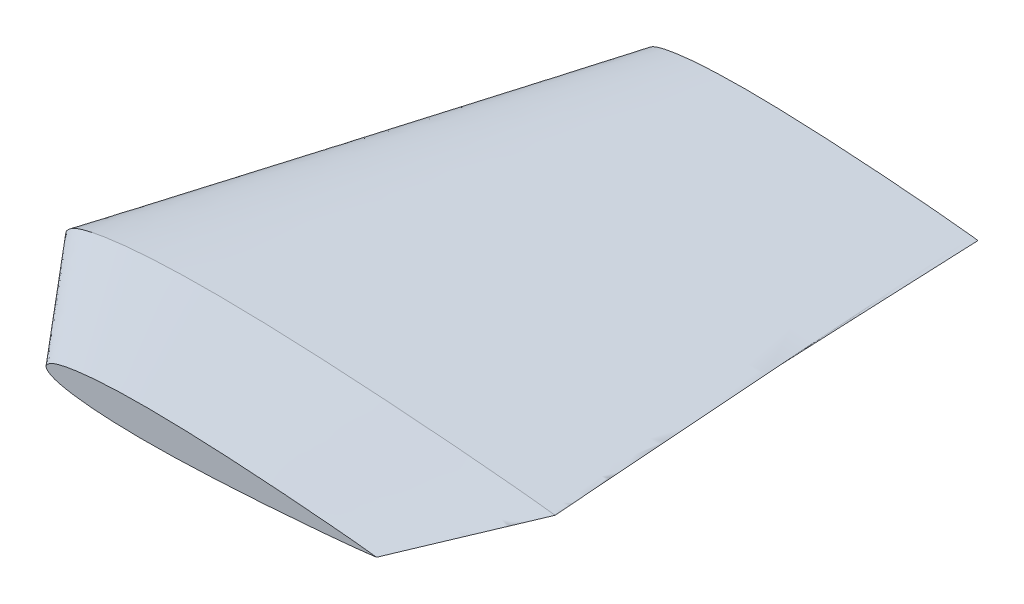
SolidWorks part; units mm, degrees
ref_plane "Front Plane" through (0, 0, 0) normal (0, 0, 1) x (1, 0, 0)
ref_plane "Top Plane" through (0, 0, 0) normal (0, 1, 0) x (1, 0, 0)
ref_plane "Right Plane" through (0, 0, 0) normal (1, 0, 0) x (0, 0, -1)
sketch "Sketch1" plane through (0, 0, 0) normal (0, 0, 1) x (1, 0, 0)
  line L0 (0, 0) -> (187.96, 0) construction
  line L1 (0, 0) -> (0, -12.4987) construction
  line L2 (0, 0) -> (-15.7902, 0) construction
  spline S0 degree 3 poles (186.243, -0.1788) (188.3915, 0) (186.243, 0.1788) (184.4821, 0.4769) (180.2047, 0.9339) (174.9493, 1.5013) (168.1015, 2.167) (160.0618, 2.9017) (150.8654, 3.6912) (140.7047, 4.5123) (129.7418, 5.3323) (118.1677, 6.1268) (106.1797, 6.8593) (93.9831, 7.4989) (81.786, 8.0074) (71.7149, 8.3011) (63.8146, 8.4361) (58.0672, 8.484) (52.4732, 8.4773) (47.0565, 8.4053) (41.8407, 8.2789) (36.8486, 8.088) (32.1012, 7.8395) (27.6181, 7.5278) (23.4185, 7.1579) (19.5216, 6.7268) (15.9436, 6.2426) (12.6986, 5.7178) (9.8001, 5.1548) (7.2575, 4.5555) (5.0828, 3.8997) (3.2807, 3.1752) (1.8678, 2.3759) (0.8518, 1.5413) (0.2172, 0.7763) (-0.0889, 0) (0.2172, -0.7763) (0.8518, -1.5413) (1.8678, -2.3759) (3.2807, -3.1752) (5.0828, -3.8997) (7.2575, -4.5555) (9.8001, -5.1548) (12.6986, -5.7178) (15.9436, -6.2426) (19.5216, -6.7268) (23.4185, -7.1579) (27.6181, -7.5278) (32.1012, -7.8395) (36.8486, -8.088) (41.8407, -8.2789) (47.0565, -8.4053) (52.4732, -8.4773) (58.0672, -8.484) (63.8146, -8.4361) (71.7149, -8.3011) (81.786, -8.0074) (93.9831, -7.4989) (106.1797, -6.8593) (118.1677, -6.1268) (129.7418, -5.3323) (140.7047, -4.5123) (150.8654, -3.6912) (160.0618, -2.9017) (168.1015, -2.167) (174.9493, -1.5013) (180.2047, -0.9339) (184.4821, -0.4769) (186.243, -0.1788) (188.3915, 0) (186.243, 0.1788) knots -0.018944 -0.008488 -0.002133 0 0.002133 0.008488 0.018944 0.033319 0.051356 0.072756 0.097141 0.124097 0.153163 0.183834 0.215589 0.247878 0.280151 0.31186 0.327333 0.342463 0.357187 0.371448 0.385183 0.398331 0.410845 0.422673 0.433769 0.44409 0.453589 0.46224 0.47001 0.476871 0.482833 0.487909 0.492155 0.495592 0.498196 0.5 0.501804 0.504408 0.507845 0.512091 0.517167 0.523129 0.52999 0.53776 0.546411 0.55591 0.566231 0.577327 0.589155 0.601669 0.614817 0.628552 0.642813 0.657537 0.672667 0.68814 0.719849 0.752122 0.784411 0.816166 0.846837 0.875903 0.902859 0.927244 0.948644 0.966681 0.981056 0.991512 0.997867 1 1.002133 1.008488 1.018944 only from (187.96, 0) to (187.96, 0)
  dimension "D1" = 187.96
ref_plane "Plane1" through (0, 0, 48.26) normal (0, 0, 1) x (1, 0, 0)
sketch "Sketch2" plane through (0, 0, 48.26) normal (0, 0, 1) x (1, 0, 0)
  line L0 (40.64, 0) -> (167.64, 0) construction
  line L1 (40.64, 0) -> (40.64, -29.8039) construction
  line L2 (40.64, 0) -> (47.4613, 0) construction
  line L3 (0, 0) -> (187.96, 0) construction
  spline S0 degree 3 poles (166.4799, -0.1208) (167.9316, 0) (166.4799, 0.1208) (165.2901, 0.3222) (162.3999, 0.631) (158.849, 1.0144) (154.2221, 1.4642) (148.7899, 1.9606) (142.5761, 2.494) (135.7108, 3.0488) (128.3034, 3.6029) (120.4831, 4.1397) (112.3831, 4.6347) (104.1421, 5.0668) (95.9008, 5.4104) (89.096, 5.6089) (83.758, 5.7) (79.8746, 5.7324) (76.0949, 5.7279) (72.4349, 5.6792) (68.9107, 5.5938) (65.5377, 5.4648) (62.33, 5.297) (59.3009, 5.0863) (56.4633, 4.8364) (53.8302, 4.5451) (51.4127, 4.218) (49.2202, 3.8634) (47.2617, 3.483) (45.5437, 3.078) (44.0743, 2.6349) (42.8567, 2.1454) (41.902, 1.6054) (41.2155, 1.0414) (40.7868, 0.5245) (40.5799, 0) (40.7868, -0.5245) (41.2155, -1.0414) (41.902, -1.6054) (42.8567, -2.1454) (44.0743, -2.6349) (45.5437, -3.078) (47.2617, -3.483) (49.2202, -3.8634) (51.4127, -4.218) (53.8302, -4.5451) (56.4633, -4.8364) (59.3009, -5.0863) (62.33, -5.297) (65.5377, -5.4648) (68.9107, -5.5938) (72.4349, -5.6792) (76.0949, -5.7279) (79.8746, -5.7324) (83.758, -5.7) (89.096, -5.6089) (95.9008, -5.4104) (104.1421, -5.0668) (112.3831, -4.6347) (120.4831, -4.1397) (128.3034, -3.6029) (135.7108, -3.0488) (142.5761, -2.494) (148.7899, -1.9606) (154.2221, -1.4642) (158.849, -1.0144) (162.3999, -0.631) (165.2901, -0.3222) (166.4799, -0.1208) (167.9316, 0) (166.4799, 0.1208) knots -0.018944 -0.008488 -0.002133 0 0.002133 0.008488 0.018944 0.033319 0.051356 0.072756 0.097141 0.124097 0.153163 0.183834 0.215589 0.247878 0.280151 0.31186 0.327333 0.342463 0.357187 0.371448 0.385183 0.398331 0.410845 0.422673 0.433769 0.44409 0.453589 0.46224 0.47001 0.476871 0.482833 0.487909 0.492155 0.495592 0.498196 0.5 0.501804 0.504408 0.507845 0.512091 0.517167 0.523129 0.52999 0.53776 0.546411 0.55591 0.566231 0.577327 0.589155 0.601669 0.614817 0.628552 0.642813 0.657537 0.672667 0.68814 0.719849 0.752122 0.784411 0.816166 0.846837 0.875903 0.902859 0.927244 0.948644 0.966681 0.981056 0.991512 0.997867 1 1.002133 1.008488 1.018944 only from (167.64, 0) to (167.64, 0)
  dimension "D1" = 127
  dimension "D2" = 40.64
ref_plane "Plane2" through (0, 0, -172.72) normal (0, 0, 1) x (1, 0, 0)
sketch "Sketch3" plane through (0, 0, -172.72) normal (0, 0, 1) x (1, 0, 0)
  line L0 (50.8, 0) -> (177.8, 0) construction
  line L1 (50.8, 0) -> (50.8, -7.5229) construction
  line L2 (50.8, 0) -> (43.7016, 0) construction
  line L3 (0, 0) -> (187.96, 0) construction
  line L5 (0, -9.3299) -> (0, 9.3299) construction
  spline S0 degree 3 poles (176.6399, -0.1208) (178.0916, 0) (176.6399, 0.1208) (175.4501, 0.3222) (172.5599, 0.631) (169.009, 1.0144) (164.3821, 1.4642) (158.9499, 1.9606) (152.7361, 2.494) (145.8708, 3.0488) (138.4634, 3.6029) (130.6431, 4.1397) (122.5431, 4.6347) (114.3021, 5.0668) (106.0608, 5.4104) (99.256, 5.6089) (93.918, 5.7) (90.0346, 5.7324) (86.2549, 5.7279) (82.5949, 5.6792) (79.0707, 5.5938) (75.6977, 5.4648) (72.49, 5.297) (69.4609, 5.0863) (66.6233, 4.8364) (63.9902, 4.5451) (61.5727, 4.218) (59.3802, 3.8634) (57.4217, 3.483) (55.7037, 3.078) (54.2343, 2.6349) (53.0167, 2.1454) (52.062, 1.6054) (51.3755, 1.0414) (50.9468, 0.5245) (50.7399, 0) (50.9468, -0.5245) (51.3755, -1.0414) (52.062, -1.6054) (53.0167, -2.1454) (54.2343, -2.6349) (55.7037, -3.078) (57.4217, -3.483) (59.3802, -3.8634) (61.5727, -4.218) (63.9902, -4.5451) (66.6233, -4.8364) (69.4609, -5.0863) (72.49, -5.297) (75.6977, -5.4648) (79.0707, -5.5938) (82.5949, -5.6792) (86.2549, -5.7279) (90.0346, -5.7324) (93.918, -5.7) (99.256, -5.6089) (106.0608, -5.4104) (114.3021, -5.0668) (122.5431, -4.6347) (130.6431, -4.1397) (138.4634, -3.6029) (145.8708, -3.0488) (152.7361, -2.494) (158.9499, -1.9606) (164.3821, -1.4642) (169.009, -1.0144) (172.5599, -0.631) (175.4501, -0.3222) (176.6399, -0.1208) (178.0916, 0) (176.6399, 0.1208) knots -0.018944 -0.008488 -0.002133 0 0.002133 0.008488 0.018944 0.033319 0.051356 0.072756 0.097141 0.124097 0.153163 0.183834 0.215589 0.247878 0.280151 0.31186 0.327333 0.342463 0.357187 0.371448 0.385183 0.398331 0.410845 0.422673 0.433769 0.44409 0.453589 0.46224 0.47001 0.476871 0.482833 0.487909 0.492155 0.495592 0.498196 0.5 0.501804 0.504408 0.507845 0.512091 0.517167 0.523129 0.52999 0.53776 0.546411 0.55591 0.566231 0.577327 0.589155 0.601669 0.614817 0.628552 0.642813 0.657537 0.672667 0.68814 0.719849 0.752122 0.784411 0.816166 0.846837 0.875903 0.902859 0.927244 0.948644 0.966681 0.981056 0.991512 0.997867 1 1.002133 1.008488 1.018944 only from (177.8, 0) to (177.8, 0)
  dimension "D1" = 127
  dimension "D2" = 50.8
loft "Loft1" add profiles "Sketch3", "Sketch1" start constraint default connector at (50.8084, 0.1012, -172.72) connector at (2.1053, 2.482, 0)
loft "Loft2" add profiles "Sketch2", "Sketch1<3>" connector at (167.6278, 0.0088, 48.26) connector at (187.96, 0, 0)
sketch "Sketch1<3>" plane through (0, 0, 0) normal (0, 0, 1) x (1, 0, 0) same geometry as "Sketch1"
